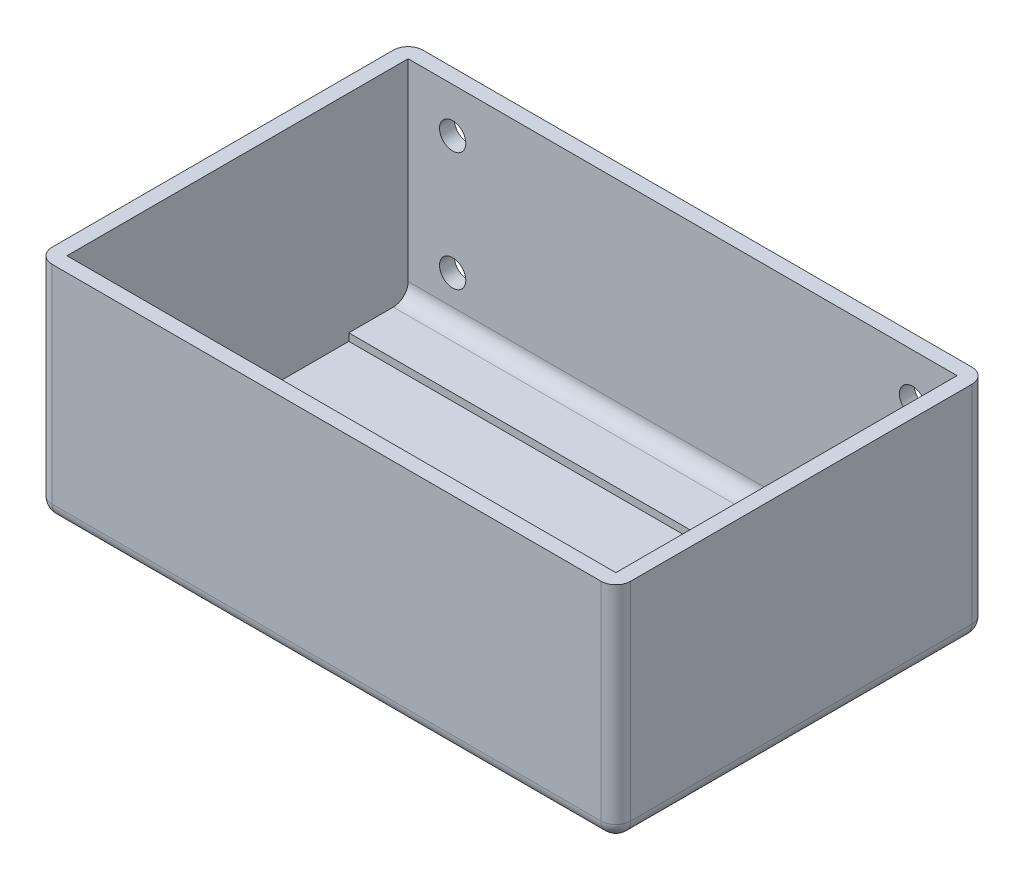
SolidWorks part; units mm, degrees
ref_plane "Front Plane" through (0, 0, 0) normal (0, 0, 1) x (1, 0, 0)
ref_plane "Top Plane" through (0, 0, 0) normal (0, 1, 0) x (1, 0, 0)
ref_plane "Right Plane" through (0, 0, 0) normal (1, 0, 0) x (0, 0, -1)
sketch "Sketch1" plane through (0, 0, 0) normal (1, 0, 0) x (0, 0, -1)
  line L0 (31.75, 0) -> (-31.75, 0)
  line L1 (-31.75, 0) -> (-31.75, 38.1)
  line L2 (-31.75, 38.1) -> (-29.21, 38.1)
  line L3 (-29.21, 38.1) -> (-29.21, 2.54)
  line L4 (-29.21, 2.54) -> (-19.05, 2.54)
  line L5 (-19.05, 2.54) -> (-19.05, 1.27)
  line L6 (-19.05, 1.27) -> (-6.35, 1.27)
  line L7 (-6.35, 1.27) -> (-6.35, 2.54)
  line L8 (-6.35, 2.54) -> (6.35, 2.54)
  line L9 (0, 2.54) -> (0, 0)
  line L10 (6.35, 1.27) -> (6.35, 2.54)
  line L11 (19.05, 1.27) -> (6.35, 1.27)
  line L12 (19.05, 2.54) -> (19.05, 1.27)
  line L13 (29.21, 2.54) -> (19.05, 2.54)
  line L14 (29.21, 38.1) -> (29.21, 2.54)
  line L15 (31.75, 38.1) -> (29.21, 38.1)
  line L16 (31.75, 0) -> (31.75, 38.1)
  dimension "D1" = 38.1
  dimension "D2" = 2.54
  dimension "D3" = 1.27
  dimension "D4" = 2.54
  dimension "D5" = 12.7
  dimension "D6" = 6.35
  dimension "D7" = 2.54
  dimension "D8" = 31.75
extrude "Boss-Extrude1" add sketch "Sketch1" along normal mid plane 96.52 contours L4 L5 L6 L7 L8 L10 L11 L12 L13 L14 L15 L16 L0 L1 L2 L3
fillet "Fillet1" radius 2.54 4 edges at (0, 0, -31.75) (0, 0, 31.75) (0, 2.54, -29.21) (0, 2.54, 29.21)
sketch "Sketch3" plane through (0, 0, 0) normal (1, 0, 0) x (0, 0, -1)
  line L0 (-31.75, 38.1) -> (-31.75, 2.54)
  line L1 (-31.75, 38.1) -> (31.75, 38.1)
  line L2 (0, 38.1) -> (0, 0)
  line L3 (29.21, 0) -> (-29.21, 0)
  line L4 (31.75, 38.1) -> (31.75, 2.54)
  arc A0 (-31.75, 2.54) -> (-29.21, 0) centre (-29.21, 2.54) ccw
  arc A1 (31.75, 2.54) -> (29.21, 0) centre (29.21, 2.54) cw
  dimension "D1" = 2.54
extrude "Boss-Extrude2" add sketch "Sketch3" along normal blind 2.54 from surface contours L0 A0 L3 L2 L1 | A1 L4 L1 L2 L3 region at (0, 19.0712, 15.8575) region at (0, 19.0712, -15.8575) starting at face at (-48.26, 9.2928, 0)
extrude "Boss-Extrude3" add sketch "Sketch3<3>" along normal blind 2.54 from surface contours A1 L4 L1 L2 L3 | L0 A0 L3 L2 L1 region at (0, 19.0712, 15.8575) region at (0, 19.0712, -15.8575) starting at face at (48.26, 9.2928, 0)
sketch "Sketch3<3>" plane through (0, 0, 0) normal (1, 0, 0) x (0, 0, -1) same geometry as "Sketch3"
sketch "Sketch4" plane through (0, 0, 0) normal (0, 0, 1) x (1, 0, 0)
  line L0 (50.8, 2.54) -> (50.8, 38.1) construction
  line L1 (50.8, 0) -> (-48.26, 0) construction
  circle A0 centre (40.64, 10.16) radius 6.35
  dimension "D1" = 12.7
  dimension "D2" = 10.16
  dimension "D3" = 10.16
extrude "Cut-Extrude2" cut sketch "Sketch4" against normal up to surface (31.75 mm away) from surface contours A0 up to face at (1.27, 20.32, -31.75) starting at face at (1.27, 21.59, -29.21)
fillet "Fillet2" radius 2.54 10 edges at (50.8, 0.7439, 31.0061) (50.8, 0, 0) (50.8, 0.7439, -31.0061) (-48.26, 0.7439, 31.0061) (-48.26, 0, 0) (-48.26, 0.7439, -31.0061) (50.8, 20.32, 31.75) (50.8, 20.32, -31.75) (-48.26, 20.32, 31.75) (-48.26, 20.32, -31.75)
hole_wizard "M4 Clearance Hole1" positions "Sketch5" profile "Sketch6" hole size "M4" standard "ISO" end condition through all
sketch "Sketch5" plane through (0, 0, -29.21) normal (0, 0, 1) x (1, 0, 0)
  line L0 (-48.26, 38.1) -> (-48.26, 2.54) construction
  line L1 (48.26, 38.1) -> (-45.72, 38.1) construction
  line L2 (50.8, 2.54) -> (50.8, 38.1) construction
  point P0 (-38.1, 30.48)
  point P2 (40.64, 30.48)
  point P4 (-38.1, 10.16)
  dimension "D1" = 10.16
  dimension "D2" = 7.62
  dimension "D3" = 20.32
  dimension "D4" = 10.16
sketch "Sketch6" plane through (-38.1, 30.48, -29.21) normal (1, 0, 0) x (0, -1, 0)
  line L0 (0, 0) -> (0, 2.54)
  line L1 (0, 2.54) -> (2.25, 2.54)
  line L2 (2.25, 2.54) -> (2.25, 0)
  line L5 (2.25, 0) -> (0, 0)
  line L11 (0, -6.35) -> (0, 107.95) construction
  dimension "Thru Hole Dia." = 4.5
  dimension "Thru Hole Depth" = 2.54
